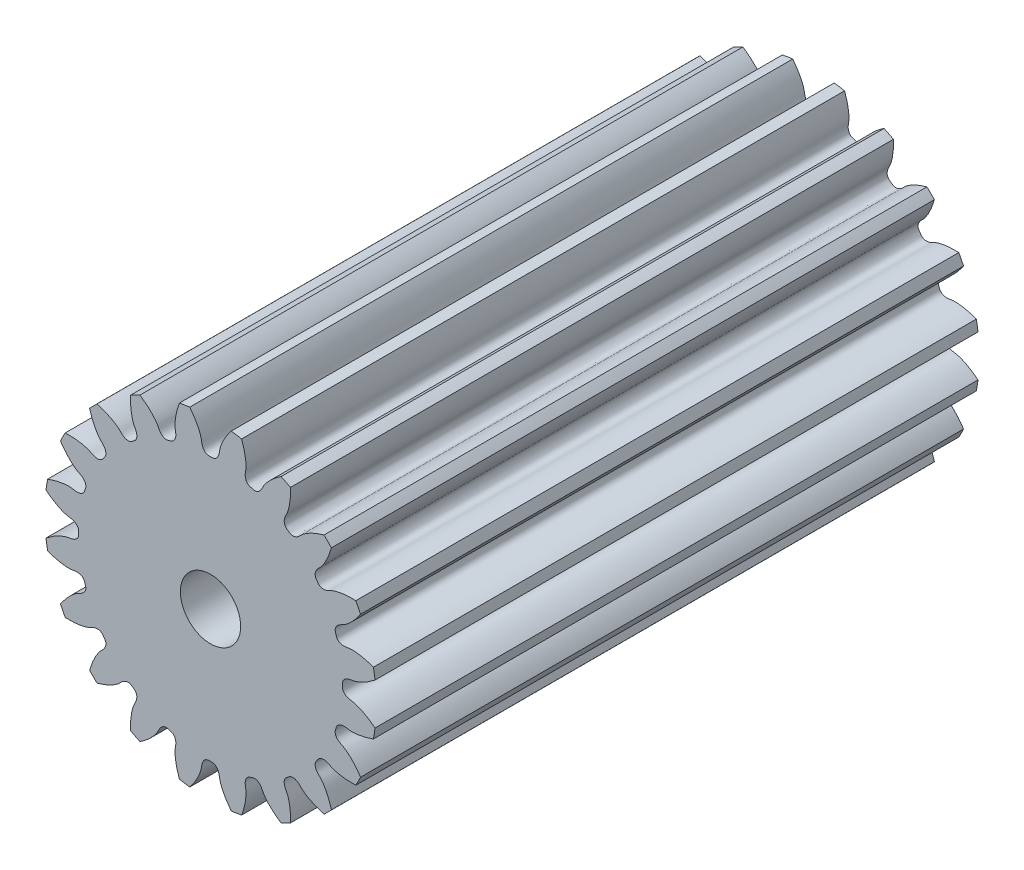
SolidWorks part; units mm, degrees
ref_plane "前视基准面" through (0, 0, 0) normal (0, 0, 1) x (1, 0, 0)
ref_plane "上视基准面" through (0, 0, 0) normal (0, 1, 0) x (1, 0, 0)
ref_plane "右视基准面" through (0, 0, 0) normal (1, 0, 0) x (0, 0, -1)
ref_axis "基准轴1" through (0, 0, 55) along (0, 0, -1)
sketch "SketchRevolveSpurGear1" plane through (0, 0, 0) normal (1, 0, 0) x (0, 0, -1)
  line L0 (0, 0) -> (1, 0) construction
  line L1 (-10, 0) -> (-10, 5.5)
  line L2 (-10, 5.5) -> (10, 5.5)
  line L3 (10, 5.5) -> (10, 0)
  line L4 (10, 0) -> (-10, 0)
revolve "SpurGear1" add sketch "SketchRevolveSpurGear1" angle 360 about L0
sketch "SketchToothSpurGear1" plane through (0, 0, 0) normal (0, 0, 1) x (1, 0, 0)
  arc A0 (5.4796, 0.7068) -> (5.4796, -0.7068) centre (0, 0) cw
  spline S0 degree 3 poles (5.4796, -0.7068) (5.4354, -0.6709) (5.3693, -0.6203) (5.2806, -0.5589) (5.2183, -0.5186) (5.1586, -0.4825) (5.1018, -0.4505) (5.048, -0.4224) (4.9974, -0.3979) (4.9502, -0.3768) (4.9065, -0.3589) (4.8665, -0.3439) (4.8303, -0.3316) (4.7981, -0.3218) (4.7699, -0.3141) (4.7458, -0.3083) (4.726, -0.3042) (4.6831, -0.2968) (4.6374, -0.2927) (4.5899, -0.2809) (4.5652, -0.2735) (4.5415, -0.265) (4.5186, -0.2551) (4.4964, -0.2437) (4.4749, -0.2304) (4.4541, -0.2149) (4.434, -0.1964) (4.4151, -0.1743) (4.3981, -0.148) (4.3844, -0.117) (4.3768, -0.0845) (4.3736, -0.045) (4.3759, 0) (4.3736, 0.045) (4.3768, 0.0845) (4.3844, 0.117) (4.3981, 0.148) (4.4151, 0.1743) (4.434, 0.1964) (4.4541, 0.2149) (4.4749, 0.2304) (4.4964, 0.2437) (4.5186, 0.2551) (4.5415, 0.265) (4.5652, 0.2735) (4.5899, 0.2809) (4.6374, 0.2927) (4.6831, 0.2968) (4.726, 0.3042) (4.7458, 0.3083) (4.7699, 0.3141) (4.7981, 0.3218) (4.8303, 0.3316) (4.8665, 0.3439) (4.9065, 0.3589) (4.9502, 0.3768) (4.9974, 0.3979) (5.048, 0.4224) (5.1018, 0.4505) (5.1586, 0.4825) (5.2183, 0.5186) (5.2806, 0.5589) (5.3693, 0.6203) (5.4354, 0.6709) (5.4796, 0.7068) knots 0 0 0 0 0.061423 0.08971 0.11638 0.141434 0.164872 0.186693 0.206898 0.225486 0.242459 0.257814 0.271554 0.283677 0.294183 0.303073 0.310347 0.316004 0.350077 0.359568 0.368803 0.377844 0.386769 0.395676 0.404689 0.413963 0.423683 0.434051 0.445256 0.457401 0.47042 0.481067 0.5 0.518933 0.52958 0.542599 0.554744 0.565949 0.576317 0.586037 0.595311 0.604324 0.613231 0.622156 0.631197 0.640432 0.649923 0.683996 0.689653 0.696927 0.705817 0.716323 0.728446 0.742186 0.757541 0.774514 0.793102 0.813307 0.835128 0.858566 0.88362 0.91029 0.938577 1 1 1 1
extrude "ToothExtrudeCutSpurGear1" cut sketch "SketchToothSpurGear1" against normal blind 10 and the other way blind 10
pattern_circular "PatternSpurGear1" count 20 over 360 about axis through (0, 0, 55) along (0, 0, -1) of "ToothExtrudeCutSpurGear1"
sketch "BoreRevolveSketch" plane through (0, 0, 0) normal (1, 0, 0) x (0, 0, -1)
  line L0 (0, 0) -> (1, 0) construction
  line L1 (-10, 0) -> (10, 0)
  line L2 (10, 0) -> (10, 1)
  line L3 (10, 1) -> (-10, 1)
  line L4 (-10, 1) -> (-10, 0)
  dimension "TaperSide1" = 1
  dimension "TaperSide2" = 1
revolve "BoreRevolveCut" cut sketch "BoreRevolveSketch" angle 360 about L0
sketch "AuxiliarySketchSpurGear1" plane through (0, 0, 0) normal (0, 0, 1) x (1, 0, 0)
  circle A0 centre (0, 0) radius 5 construction
  circle A1 centre (0, 0) radius 4.6985 construction
  circle A2 centre (0, 0) radius 4.7016 construction
  circle A3 centre (0, 0) radius 5.5 construction
  circle A4 centre (0, 0) radius 4.375 construction
  dimension "PitchDiameter" = 10
  dimension "BaseDiameter" = 9.3969
  dimension "FormDiameter" = 9.4032
  dimension "MajorDiameter" = 11
  dimension "MinorDiameter" = 8.75
